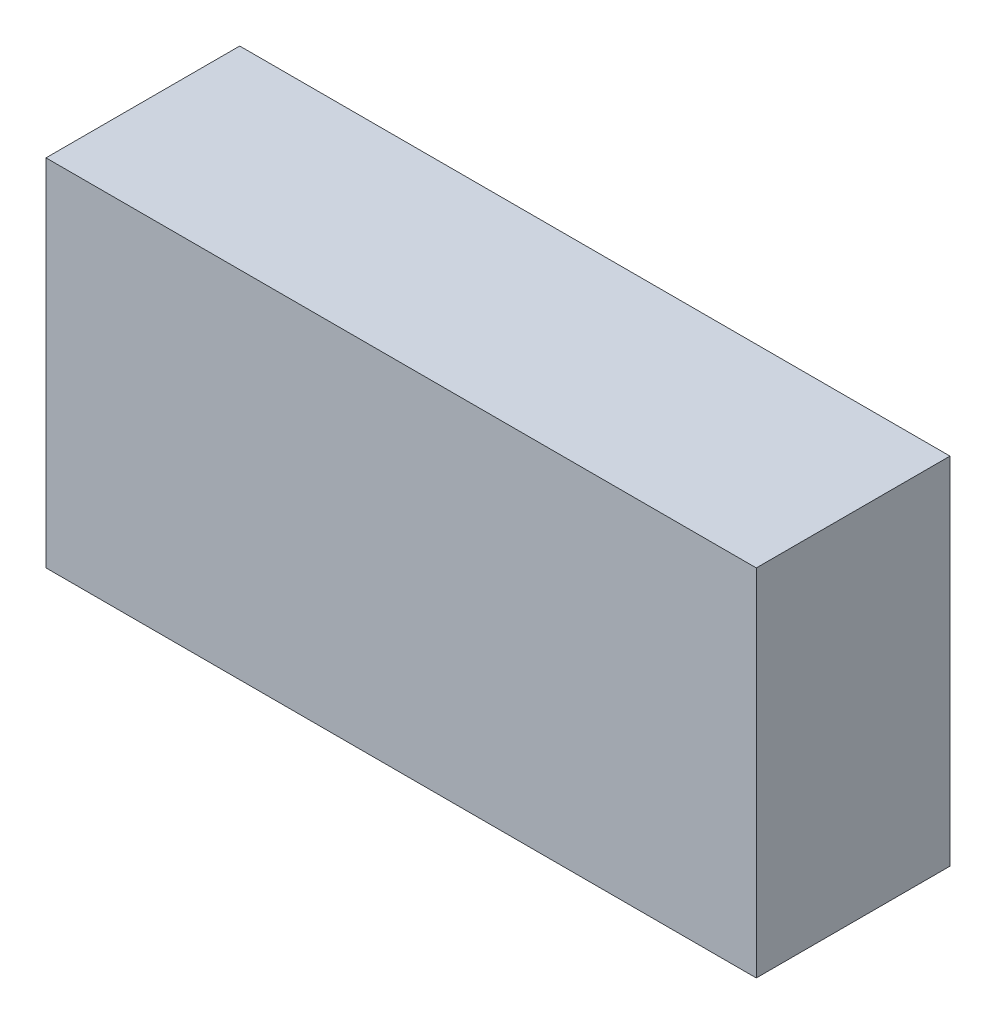
SolidWorks part; units mm, degrees
material "Silicon"
ref_plane "Front Plane" through (0, 0, 0) normal (0, 0, 1) x (1, 0, 0)
ref_plane "Top Plane" through (0, 0, 0) normal (0, 1, 0) x (1, 0, 0)
ref_plane "Right Plane" through (0, 0, 0) normal (1, 0, 0) x (0, 0, -1)
sketch "Sketch1" plane through (0, 0, 0) normal (0, 0, 1) x (1, 0, 0)
  line L1 (-49.0607, 24.571) -> (60.9393, 24.571)
  line L2 (-49.0607, 24.571) -> (-49.0607, -30.429)
  line L3 (-49.0607, -30.429) -> (60.9393, -30.429)
  line L4 (60.9393, 24.571) -> (60.9393, -30.429)
  dimension "D1" = 110
  dimension "D2" = 55
extrude "Boss-Extrude1" add sketch "Sketch1" along normal blind 30
